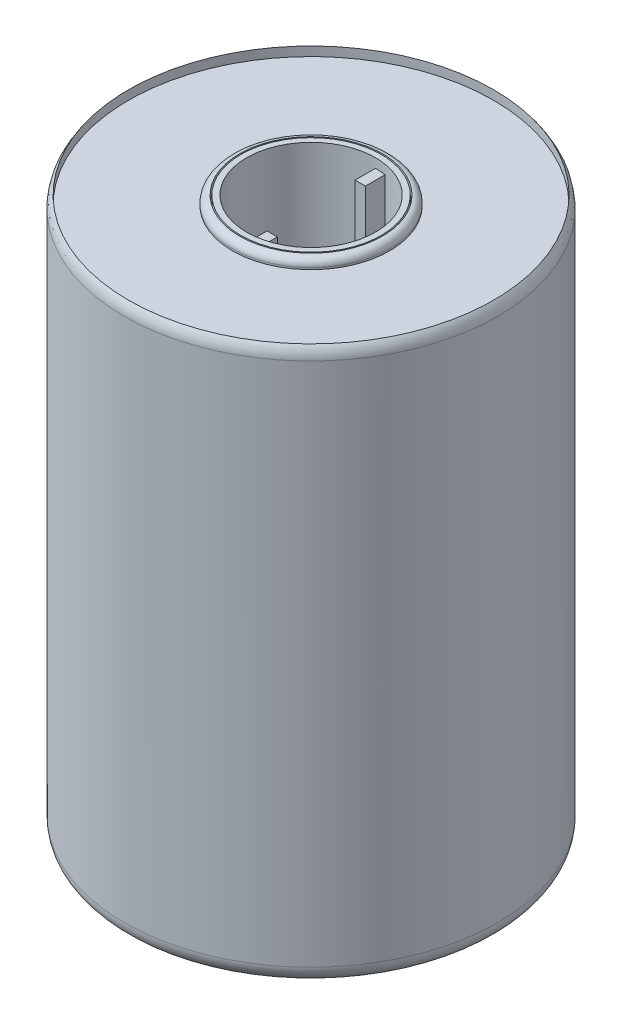
SolidWorks part; units mm, degrees
ref_plane "Alzado" through (0, 0, 0) normal (0, 0, 1) x (1, 0, 0)
ref_plane "Planta" through (0, 0, 0) normal (0, 1, 0) x (1, 0, 0)
ref_plane "Vista lateral" through (0, 0, 0) normal (1, 0, 0) x (0, 0, -1)
sketch "Croquis1" plane through (0, 0, 0) normal (0, 1, 0) x (1, 0, 0)
  circle A0 centre (0, 0) radius 50.8901
extrude "Saliente-Extruir1" add sketch "Croquis1" along normal blind 150
sketch "Croquis2" plane through (0, 150, 0) normal (0, 1, 0) x (1, 0, 0)
  circle A0 centre (0, 0) radius 17.5714
extrude "Cortar-Extruir1" cut sketch "Croquis2" against normal through all
sketch "Croquis3" plane through (0, 150, 0) normal (0, 1, 0) x (1, 0, 0)
  circle A0 centre (0, 0) radius 19.1218
  circle A1 centre (0, 0) radius 49.7184
extrude "Cortar-Extruir2" cut sketch "Croquis3" against normal blind 2.5
sketch "Croquis4" plane through (0, 0, 0) normal (0, -1, 0) x (1, 0, 0)
  circle A0 centre (0, 0) radius 17.8298
  circle A1 centre (0, 0) radius 19.4769
extrude "Saliente-Extruir3" add sketch "Croquis4" along normal blind 15
sketch "Croquis6" plane through (0, 0, 0) normal (0, -1, 0) x (1, 0, 0)
  circle A0 centre (0, 0) radius 21.5317
  circle A1 centre (0, 0) radius 49.2332
extrude "Cortar-Extruir4" cut sketch "Croquis6" against normal blind 5
sketch "Croquis8" plane through (0, 147.5, 0) normal (0, 1, 0) x (1, 0, 0)
  line L1 (0, 17.5714) -> (2.814, 17.5714)
  line L2 (0, 17.5714) -> (0, 11.9953)
  line L3 (0, 11.9953) -> (2.814, 11.9953)
  line L4 (2.814, 17.5714) -> (2.814, 11.9953)
  line L5 (0, -17.5714) -> (2.814, -17.5714)
  line L6 (0, -17.5714) -> (0, -11.9953)
  line L7 (0, -11.9953) -> (2.814, -11.9953)
  line L8 (2.814, -17.5714) -> (2.814, -11.9953)
  circle A0 centre (0, 0) radius 17.5714 construction
  point P10 (0, 0)
  point P11 (0, 0)
  point P12 (0, 0)
extrude "Saliente-Extruir6" add sketch "Croquis8" against normal blind 145
sketch "Croquis9" plane through (0, 147.5, 0) normal (0, 1, 0) x (1, 0, 0)
  circle A0 centre (0, 0) radius 19.463
  circle A1 centre (0, 0) radius 21.4211
extrude "Saliente-Extruir7" add sketch "Croquis9" along normal blind 2.5
fillet "Redondeo1" radius 5 1 edges at (0, 0, 50.8901)
fillet "Redondeo2" radius 5 1 edges at (0, -15, -19.4769)
fillet "Redondeo3" radius 5 1 edges at (0, 0, -21.5317)
fillet "Redondeo4" radius 5 1 edges at (0, 150, 50.8901)
fillet "Redondeo6" radius 2 1 edges at (0, 150, 21.4211)
